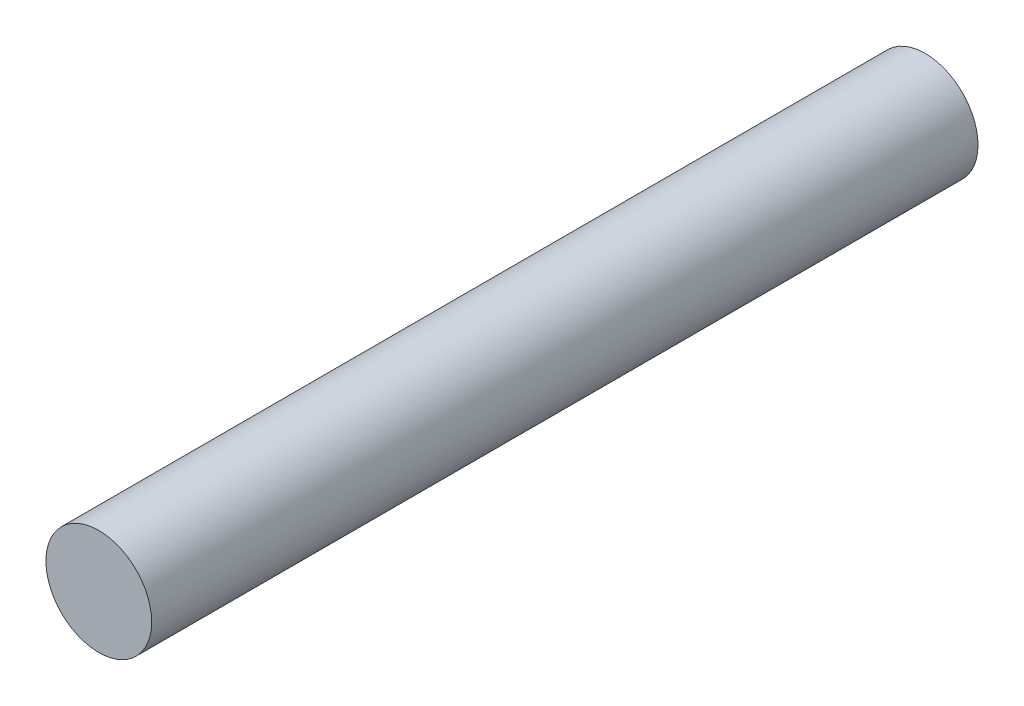
SolidWorks part; units mm, degrees
ref_plane "Front Plane" through (0, 0, 0) normal (0, 0, 1) x (1, 0, 0)
ref_plane "Top Plane" through (0, 0, 0) normal (0, 1, 0) x (1, 0, 0)
ref_plane "Right Plane" through (0, 0, 0) normal (1, 0, 0) x (0, 0, -1)
sketch "Esquisse1" plane through (0, 0, 0) normal (0, 0, 1) x (1, 0, 0)
  circle A0 centre (0, 0) radius 1.6
  dimension "D1" = 3.2
extrude "Main" add sketch "Esquisse1" along normal blind 25
